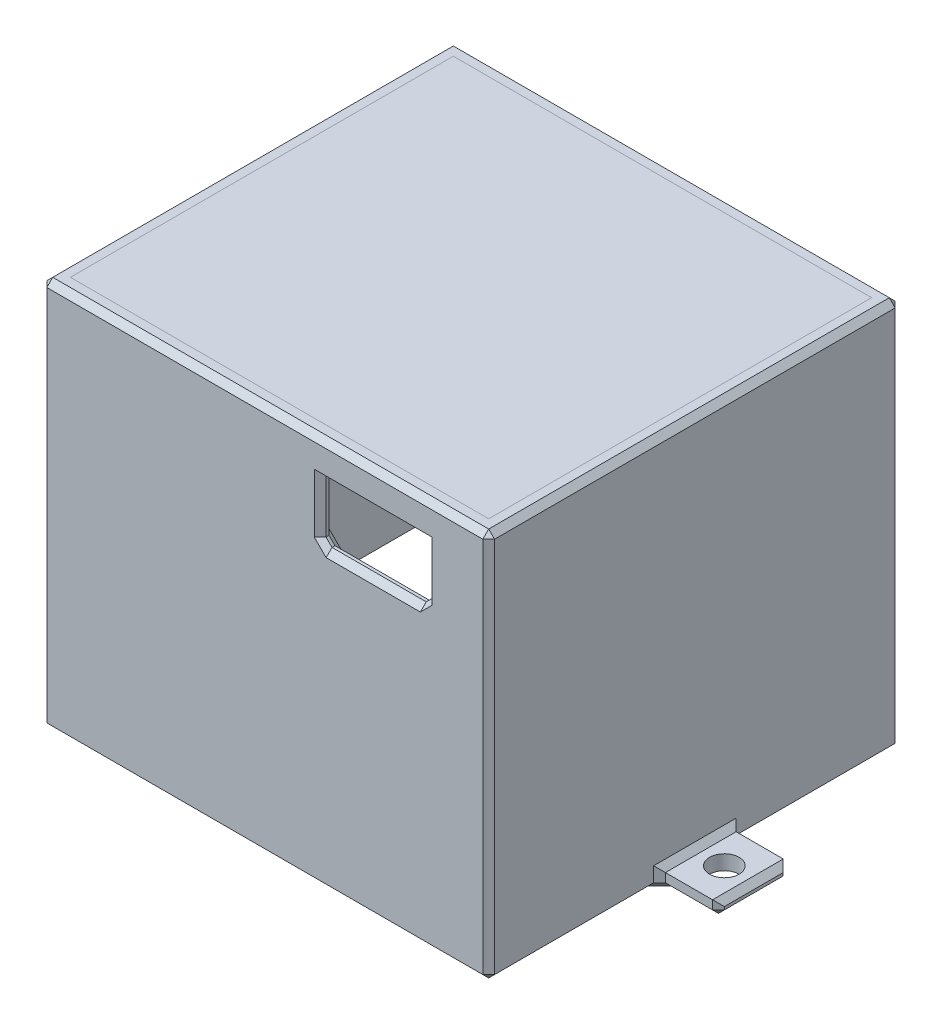
SolidWorks part; units mm, degrees
ref_plane "前视基准面" through (0, 0, 0) normal (0, 0, 1) x (1, 0, 0)
ref_plane "上视基准面" through (0, 0, 0) normal (0, 1, 0) x (1, 0, 0)
ref_plane "右视基准面" through (0, 0, 0) normal (1, 0, 0) x (0, 0, -1)
other "Configuration Table"
sketch "草图1" plane through (0, 0, 0) normal (0, 1, 0) x (1, 0, 0)
  line L1 (0, 0) -> (70, 0)
  line L2 (0, 0) -> (0, -64)
  line L3 (0, -64) -> (70, -64)
  line L4 (70, 0) -> (70, -64)
  dimension "D1" = 70
  dimension "D2" = 64
extrude "凸台-拉伸1" add sketch "草图1" along normal blind 6
sketch "草图2" plane through (0, 0, 0) normal (0, -1, 0) x (1, 0, 0)
  line L8 (-0.5, 64.5) -> (-0.5, -0.5)
  line L9 (-0.5, -0.5) -> (70.5, -0.5)
  line L10 (70.5, -0.5) -> (70.5, 64.5)
  line L11 (70.5, 64.5) -> (-0.5, 64.5)
  line L12 (-0.5, 64.5) -> (-0.5, -0.5)
  line L13 (-0.5, -0.5) -> (70.5, -0.5)
  line L14 (70.5, -0.5) -> (70.5, 64.5)
  line L15 (70.5, 64.5) -> (-0.5, 64.5)
  line L20 (-3, 67) -> (-3, -3)
  line L21 (-3, -3) -> (73, -3)
  line L22 (73, -3) -> (73, 67)
  line L23 (73, 67) -> (-3, 67)
  line L24 (-3, 67) -> (-3, -3)
  line L25 (-3, -3) -> (73, -3)
  line L26 (73, -3) -> (73, 67)
  line L27 (73, 67) -> (-3, 67)
  line L32 (3, 61) -> (3, 3)
  line L33 (67, 61) -> (3, 61)
  line L34 (67, 3) -> (67, 61)
  line L35 (3, 3) -> (67, 3)
  line L36 (3, 61) -> (3, 3)
  line L37 (67, 61) -> (3, 61)
  line L38 (67, 3) -> (67, 61)
  line L39 (3, 3) -> (67, 3)
  line L44 (0, 64) -> (0, 0)
  line L45 (70, 64) -> (0, 64)
  line L46 (70, 0) -> (70, 64)
  line L47 (0, 0) -> (70, 0)
  line L48 (0, 64) -> (0, 0)
  line L49 (70, 64) -> (0, 64)
  line L50 (70, 0) -> (70, 64)
  line L51 (0, 0) -> (70, 0)
  line M17 (0, 64) -> (0, 0)
  line M18 (0, 0) -> (70, 0)
  line M19 (70, 0) -> (70, 64)
  line M20 (70, 64) -> (0, 64)
  dimension "D1" = 0.5
  dimension "D2" = 3
  dimension "D3" = 3
  dimension "D4" = 0
extrude "凸台-拉伸2" add sketch "草图2" against normal blind 6 contours L14 L15 L12 L13 M17 M20 M19 M18 region at (35, 0, 64.4037)
extrude "凸台-拉伸3" add sketch "草图2<4>" along normal blind 60 and the other way blind 6 separate body contours L26 L27 L24 L25 L15 L14 L13 L12 region at (35, 0, 65.9668)
sketch "草图2<4>" plane through (0, 0, 0) normal (0, -1, 0) x (1, 0, 0) same geometry as "草图2"
sketch "草图6" plane through (0, 0, -3) normal (0, 0, -1) x (-1, 0, 0)
  line L0 (0.5, 0) -> (-70.5, 0) construction
  line L1 (-62.4063, 0) -> (-44.4063, 0)
  line L2 (-62.4063, 0) -> (-62.4063, -10)
  line L3 (-62.4063, -10) -> (-44.4063, -10)
  line L4 (-44.4063, 0) -> (-44.4063, -10)
  dimension "D1" = 10
  dimension "19" = 18
extrude "切除-拉伸2" cut sketch "草图6" against normal blind 117
sketch "草图7" plane through (0, -60, 0) normal (0, -1, 0) x (1, 0, 0)
  line L0 (-3, 67) -> (-3, -3) construction
  line L1 (-3, 32) -> (-13, 32) construction
  line L2 (-3, 26) -> (-3, 38)
  line L3 (-3, 38) -> (-13, 38)
  line L4 (-13, 26) -> (-13, 38)
  line L5 (35, 64.5) -> (35, -0.5) construction
  line L6 (70.5, 64.5) -> (-0.5, 64.5) construction
  line L7 (-0.5, -0.5) -> (70.5, -0.5) construction
  line L8 (-3, 26) -> (-13, 26)
  line L9 (-13, 32) -> (-3, 32) construction
  line L13 (-3, 38) -> (-13, 38)
  line L14 (-3, 26) -> (-13, 26)
  line L15 (-3, 38) -> (-13, 38)
  line L16 (-3, 26) -> (-13, 26)
  line L17 (-3, 38) -> (-13, 38)
  line L18 (-3, 26) -> (-13, 26)
  line L19 (-3, 38) -> (-13, 38)
  line L20 (-3, 26) -> (-13, 26)
  line L21 (-3, 38) -> (-13, 38)
  line L22 (-3, 26) -> (-13, 26)
  line L23 (-3, 38) -> (-13, 38)
  line L24 (-3, 26) -> (-13, 26)
  line L25 (-3, 38) -> (-13, 38)
  line L26 (-3, 26) -> (-13, 26)
  line L27 (73, 32) -> (83, 32) construction
  line L28 (73, 26) -> (83, 26)
  line L29 (73, 38) -> (83, 38)
  line L30 (73, 26) -> (83, 26)
  line L31 (73, 38) -> (83, 38)
  line L32 (73, 26) -> (83, 26)
  line L33 (73, 38) -> (83, 38)
  line L34 (73, 26) -> (83, 26)
  line L35 (73, 38) -> (83, 38)
  line L36 (73, 26) -> (83, 26)
  line L37 (73, 38) -> (83, 38)
  line L38 (73, 26) -> (83, 26)
  line L39 (73, 38) -> (83, 38)
  line L40 (73, 26) -> (83, 26)
  line L41 (73, 38) -> (83, 38)
  line L42 (83, 32) -> (73, 32) construction
  line L43 (73, 26) -> (83, 26)
  line L44 (83, 26) -> (83, 38)
  line L45 (73, 38) -> (83, 38)
  line L46 (73, 26) -> (73, 38)
  circle A0 centre (-8, 32) radius 2.5
  circle A1 centre (78, 32) radius 2.5
  line M14 (73, -3) -> (73, 67)
  line M16 (-3, 67) -> (-3, -3)
  dimension "D3" = 5
  dimension "D1" = 10
  dimension "D2" = 12
extrude "凸台-拉伸4" add sketch "草图7" against normal blind 2.5 contours L8 L3 L4 A0 M16 | L28 L44 L29 A1 M14 region at (-8, -60, 26.1562) region at (73.1562, -60, 32)
chamfer "倒角1" distance 1 angle 45 53 edges at (-8, -60, 26) (-8, -60, 38) (78, -60, 38) (78, -60, 26) (-3, -60, 11.5) (-3, 6, 32) (-3, -58.75, 26) (-3, -57.5, 32) (-3, -58.75, 38) (-3, -60, 52.5) (35, 6, 67) (-3, -27, 67) (35, -60, 67) (73, -60, 52.5) (73, -27, 67) (73, 6, 32) (73, -58.75, 38) (73, -57.5, 32) (73, -58.75, 26) (73, -60, 11.5) (35, 6, -3) (-3, -27, -3) (35, -60, -3) (73, -27, -3) (-13, -58.75, 26) (-13, -57.5, 32) (-13, -58.75, 38) (-13, -60, 32) (83, -58.75, 38) (83, -57.5, 32) (83, -58.75, 26) (83, -60, 32) (44.4063, -5, 64.5) (62.4063, -5, 64.5) (53.4063, 0, 67) (44.4063, -5, 67) (62.4063, -5, 67) (53.4063, -10, 64.5) (62.4063, -10, 65.75) (53.4063, -10, 67) (44.4063, -10, 65.75) (53.4063, -10, -0.5) (44.4063, -10, -1.75) (53.4063, -10, -3) (62.4063, -10, -1.75) (44.4063, -5, -0.5) (62.4063, -5, -0.5) (62.4063, -5, -3) (44.4063, -5, -3) (53.4063, 0, -0.5) (62.4063, 0, -1.75) (53.4063, 0, -3) (44.4063, 0, -1.75)
